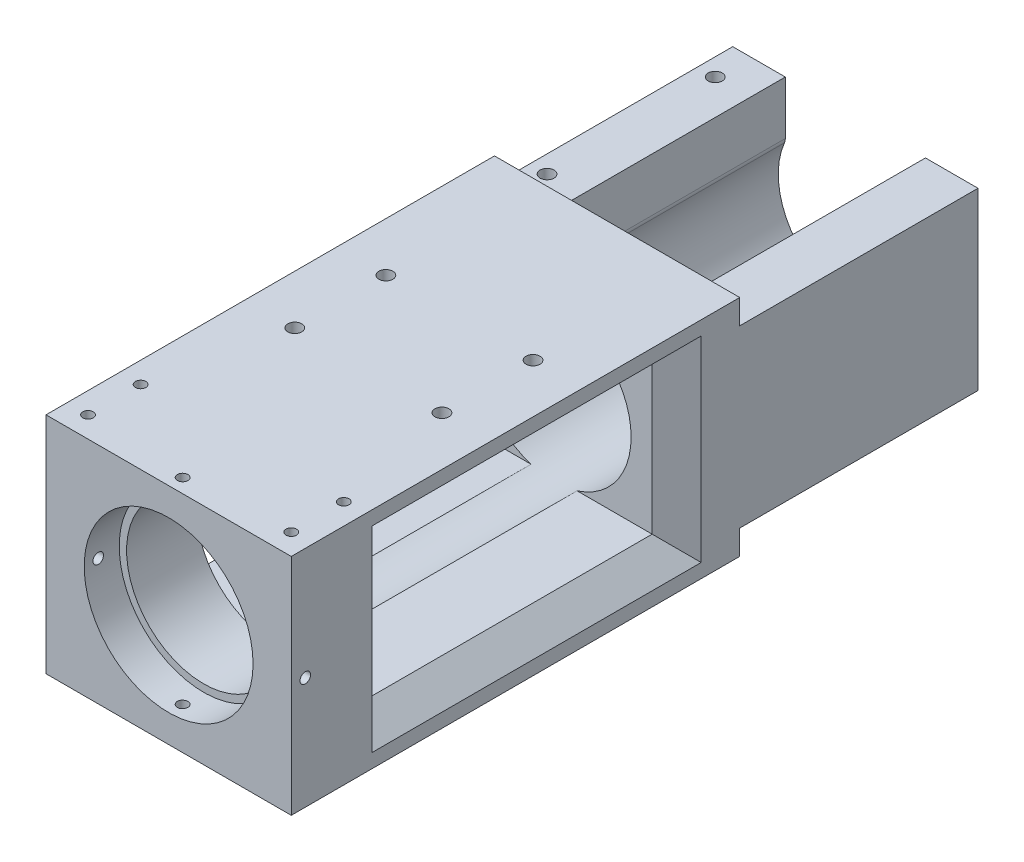
SolidWorks part; units mm, degrees
material "1060-O (SS)"
ref_plane "前视基准面" through (0, 0, 0) normal (0, 0, 1) x (1, 0, 0)
ref_plane "上视基准面" through (0, 0, 0) normal (0, 1, 0) x (1, 0, 0)
ref_plane "右视基准面" through (0, 0, 0) normal (1, 0, 0) x (0, 0, -1)
sketch "草图1" plane through (0, 0, 0) normal (0, 0, 1) x (1, 0, 0)
  line L1 (-35, -32) -> (35, -32)
  line L2 (-35, -32) -> (-35, 32)
  line L3 (-35, 32) -> (35, 32)
  line L4 (35, -32) -> (35, 32)
  line L5 (-35, -32) -> (35, 32) construction
  line L6 (-35, 32) -> (35, -32) construction
  point P0 (0, 0)
  dimension "D1" = 70
  dimension "D2" = 64
extrude "凸台-拉伸1" add sketch "草图1" along normal mid plane 140
sketch "草图2" plane through (0, 0, 70) normal (0, 0, 1) x (1, 0, 0)
  circle A0 centre (0, 0) radius 24.1
  dimension "D1" = 48.2
extrude "切除-拉伸1" cut sketch "草图2" against normal blind 10
sketch "草图3" plane through (0, 32, 0) normal (0, 1, 0) x (1, 0, 0)
  line L0 (35, -70) -> (-35, -70) construction
  circle A0 centre (0, -66) radius 1.5
  point P5 (0, -70)
  dimension "D1" = 3
  dimension "D2" = 4
extrude "切除-拉伸2" cut sketch "草图3" against normal through all
sketch "草图4" plane through (35, 0, 0) normal (1, 0, 0) x (0, 0, -1)
  line L0 (-70, -32) -> (-70, 32) construction
  circle A0 centre (-66, 0) radius 1.5
  dimension "D1" = 3
  dimension "D2" = 4
extrude "切除-拉伸3" cut sketch "草图4" against normal through all
sketch "草图5" plane through (0, 0, 60) normal (0, 0, 1) x (1, 0, 0)
  circle A0 centre (0, 0) radius 22
  dimension "D1" = 44
extrude "切除-拉伸4" cut sketch "草图5" against normal through all
sketch "草图6" plane through (35, 0, 0) normal (1, 0, 0) x (0, 0, -1)
  line L1 (-40, -21) -> (40, -21)
  line L2 (-40, -21) -> (-40, 21)
  line L3 (-40, 21) -> (40, 21)
  line L4 (40, -21) -> (40, 21)
  line L5 (-40, -21) -> (40, 21) construction
  line L6 (-40, 21) -> (40, -21) construction
  point P0 (0, 0)
  dimension "D1" = 42
  dimension "D2" = 80
extrude "切除-拉伸5" cut sketch "草图6" against normal through all
chamfer "倒角1" distance 7 angle 45 8 edges at (-35, 0, -40) (-35, -21, 0) (-35, 0, 40) (-35, 21, 0) (35, 21, 0) (35, 0, -40) (35, 0, 40) (35, -21, 0)
sketch "草图7" plane through (0, 32, 0) normal (0, 1, 0) x (1, 0, 0)
  line L0 (-21, 13) -> (21, 13) construction
  circle A0 centre (-21, 13) radius 2
  circle A1 centre (21, 13) radius 2
  point P4 (0, 13)
  dimension "D1" = 4
  dimension "D2" = 42
  dimension "D3" = 13
extrude "切除-拉伸6" cut sketch "草图7" against normal blind 20
sketch "草图8" plane through (0, 21, 0) normal (0, -1, 0) x (1, 0, 0)
  circle A1 centre (21, -13) radius 2 construction
  circle A2 centre (21, -13) radius 5.5
  circle A3 centre (21, -13) radius 5.5
  circle A4 centre (21, -13) radius 2
  circle M2 centre (21, -13) radius 2
  dimension "D1" = 3.5
extrude "切除-拉伸7" cut sketch "草图8" against normal blind 7 contours A3 M2 region at (15.6556, 21, -13)
mirror "镜向1" about plane through (0, 0, 0) normal (1, 0, 0) of "切除-拉伸7"
mirror "镜向2" about plane through (0, 0, 0) normal (0, 0, 1) of "镜向1", "切除-拉伸7", "切除-拉伸6"
sketch "草图9" plane through (0, 0, 0) normal (1, 0, 0) x (0, 0, -1)
  line L0 (-112.2479, 0) -> (108.0194, 0)
sketch "草图10" plane through (0, 0, -70) normal (0, 0, -1) x (-1, 0, 0)
  circle A0 centre (0, 0) radius 22 construction
  point P0 (0, -22)
sketch "草图11" plane through (0, 32, 0) normal (0, 1, 0) x (1, 0, 0)
  line L0 (-29, -64) -> (29, -64) construction
  line L1 (35, -70) -> (-35, -70) construction
  line L2 (-29, -49) -> (29, -49) construction
  circle A0 centre (-29, -64) radius 1.5
  circle A1 centre (29, -64) radius 1.5
  circle A2 centre (-29, -49) radius 1.5
  circle A3 centre (29, -49) radius 1.5
  point P4 (0, -64)
  point P7 (0, -70)
  point P12 (0, -49)
  dimension "D3" = 3
  dimension "D1" = 58
  dimension "D2" = 6
  dimension "D4" = 15
extrude "切除-拉伸8" cut sketch "草图11" against normal blind 10
sketch "草图12" plane through (35, 0, 0) normal (1, 0, 0) x (0, 0, -1)
  line L0 (-70, -32) -> (70, -32) construction
  line L1 (58, -32) -> (70, -32)
  line L2 (58, -32) -> (58, 32)
  line L3 (58, 32) -> (70, 32)
  line L4 (70, -32) -> (70, 32)
  line L5 (58, -32) -> (70, 32) construction
  line L6 (58, 32) -> (70, -32) construction
  point P0 (64, 0)
  point P6 (64, -32)
  dimension "D2" = 12
extrude "切除-拉伸9" cut sketch "草图12" against normal through all
sketch "草图13" plane through (0, 0, -58) normal (0, 0, -1) x (-1, 0, 0)
  line L0 (35, 32) -> (35, -32) construction
  line L1 (-35, -25) -> (35, -25)
  line L2 (-35, -25) -> (-35, 25)
  line L3 (-35, 25) -> (35, 25)
  line L4 (35, -25) -> (35, 25)
  line L5 (-35, -25) -> (35, 25) construction
  line L6 (-35, 25) -> (35, -25) construction
  circle A0 centre (0, 0) radius 22 construction
  circle A1 centre (0, 0) radius 22
  point P0 (0, 0)
  dimension "D1" = 50
extrude "凸台-拉伸2" add sketch "草图13" along normal blind 68
sketch "草图14" plane through (0, 25, 0) normal (0, 1, 0) x (1, 0, 0)
  line L0 (-35, 58) -> (35, 58) construction
  line L1 (20, 126) -> (-20, 126)
  line L2 (20, 126) -> (20, 58)
  line L3 (20, 58) -> (-20, 58)
  line L4 (-20, 126) -> (-20, 58)
  line L5 (20, 126) -> (-20, 58) construction
  line L6 (20, 58) -> (-20, 126) construction
  line L7 (-35, 126) -> (35, 126) construction
  point P0 (0, 92)
  point P7 (0, 126)
  point P10 (0, 0)
  point P12 (0, 58)
  dimension "D1" = 40
extrude "切除-拉伸10" cut sketch "草图14" against normal blind 20
fillet "圆角1" radius 3 2 edges at (-20, 9.1652, -92) (20, 9.1652, -92)
sketch "草图15" plane through (0, 25, 0) normal (0, 1, 0) x (1, 0, 0)
  line L0 (-30, 68) -> (-30, 116) construction
  line L1 (-35, 126) -> (-35, 58) construction
  line L2 (-35, 126) -> (-20, 126) construction
  circle A0 centre (-30, 68) radius 2
  circle A1 centre (-30, 116) radius 2
  dimension "D1" = 4
  dimension "D2" = 48
  dimension "D3" = 5
  dimension "D4" = 10
extrude "切除-拉伸11" cut sketch "草图15" against normal blind 10 contours A1 | A0 region at (-30, 25, -116)
